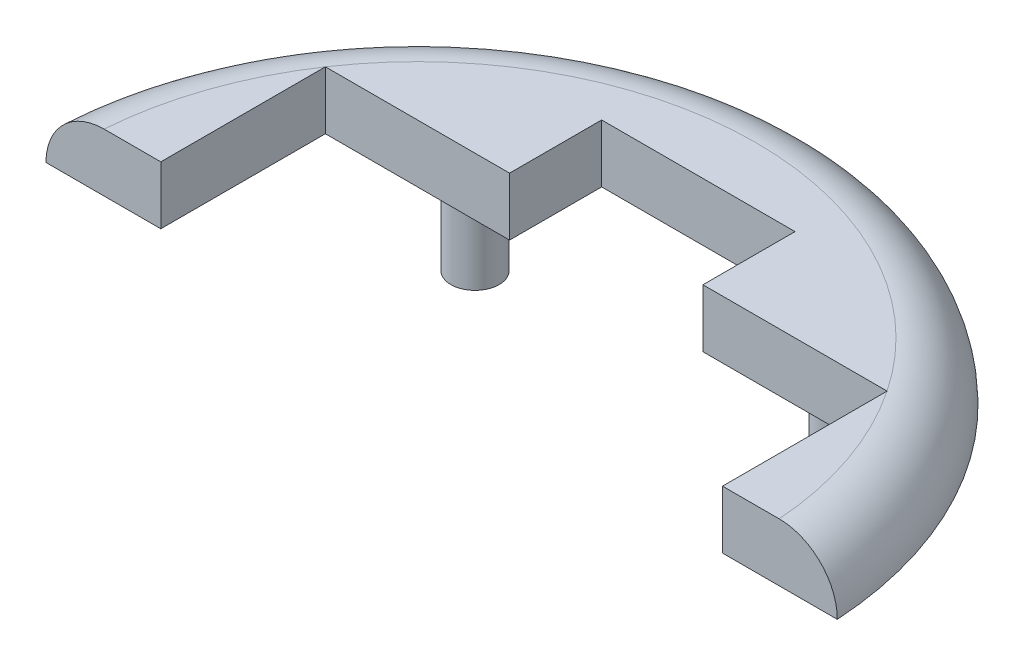
SolidWorks part; units mm, degrees
ref_plane "Front Plane" through (0, 0, 0) normal (0, 0, 1) x (1, 0, 0)
ref_plane "Top Plane" through (0, 0, 0) normal (0, 1, 0) x (1, 0, 0)
ref_plane "Right Plane" through (0, 0, 0) normal (1, 0, 0) x (0, 0, -1)
sketch "Sketch1" plane through (0, 0, 0) normal (0, 1, 0) x (1, 0, 0)
  line L0 (-20.3358, 2.5) -> (10100.8159, 2.5) construction
  line L1 (-40.9237, 2.5) -> (-29.05, 2.5)
  line L2 (40.9237, 2.5) -> (29.05, 2.5)
  line L3 (29.05, 2.5) -> (29.05, 19.525)
  line L4 (29.05, 19.525) -> (10, 19.525)
  line L5 (10, 19.525) -> (10, 29.05)
  line L6 (10, 29.05) -> (-10, 29.05)
  line L7 (-10, 29.05) -> (-10, 19.525)
  line L8 (-10, 19.525) -> (-29.05, 19.525)
  line L9 (-29.05, 19.525) -> (-29.05, 2.5)
  arc A0 (-40.9237, 2.5) -> (40.9237, 2.5) centre (0, 0) cw
  point P16 (10.7608, -2.8221)
  dimension "D2" = 41
  dimension "D1" = 2.5
  dimension "D3" = 29.05
  dimension "D4" = 29.05
  dimension "D5" = 17.025
  dimension "D6" = 29.05
  dimension "D7" = 20
  dimension "D8" = 10
  dimension "D9" = 17.025
extrude "Boss-Extrude1" add sketch "Sketch1" along normal blind 6
fillet "Fillet1" radius 6 1 edges at (0, 6, -41)
sketch "Sketch2" plane through (0, 0, 0) normal (0, -1, 0) x (1, 0, 0)
  circle A0 centre (19.05, -25) radius 2.5
  circle A1 centre (-19.05, -25) radius 2.5
  circle A2 centre (19.05, -25) radius 0.8
  circle A3 centre (-19.05, -25) radius 0.8
  dimension "D5" = 5
  dimension "D6" = 5
  dimension "D7" = 1.6
  dimension "D8" = 1.6
  dimension "D1" = 19.05
  dimension "D2" = 25
  dimension "D3" = 19.05
  dimension "D4" = 25
extrude "Boss-Extrude2" add sketch "Sketch2" along normal blind 10
